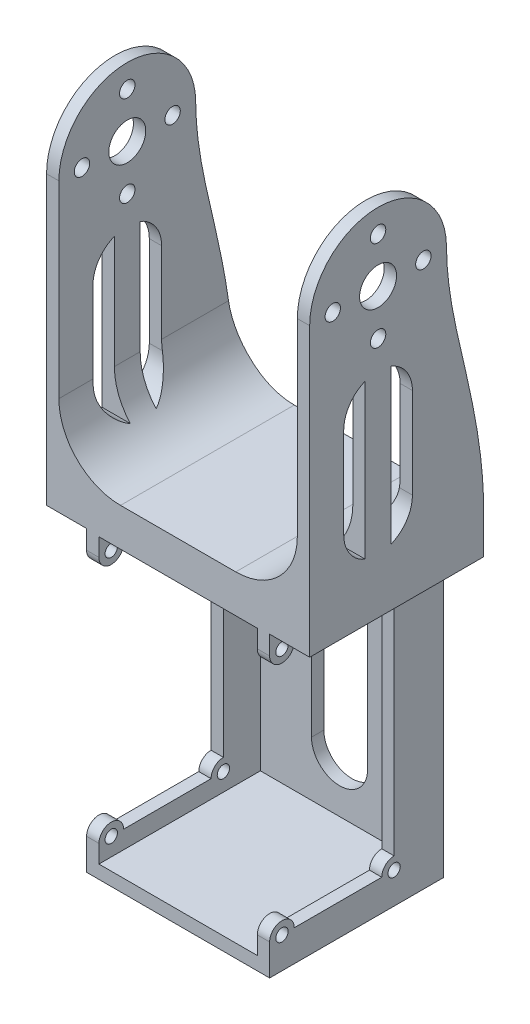
SolidWorks part; units mm, degrees
ref_plane "前视基准面" through (0, 0, 0) normal (0, 0, 1) x (1, 0, 0)
ref_plane "上视基准面" through (0, 0, 0) normal (0, 1, 0) x (1, 0, 0)
ref_plane "右视基准面" through (0, 0, 0) normal (1, 0, 0) x (0, 0, -1)
other "Configuration Table"
sketch "草图1" plane through (0, 0, 0) normal (0, 1, 0) x (1, 0, 0)
  line L0 (0, 10.5) -> (0, -10.5) construction
  line L1 (-21.35, 10.5) -> (21.35, 10.5)
  line L2 (-21.35, 10.5) -> (-21.35, -10.5)
  line L3 (-21.35, -10.5) -> (21.35, -10.5)
  line L4 (21.35, 10.5) -> (21.35, -10.5)
  line L5 (-21.35, 10.5) -> (21.35, -10.5) construction
  line L6 (-21.35, -10.5) -> (21.35, 10.5) construction
  line L7 (-21.35, 0) -> (21.35, 0) construction
  line L8 (8.018, 1.5509) -> (12.9126, 1.5509)
  line L9 (8.018, -1.5509) -> (12.9126, -1.5509)
  line L10 (-8.018, -1.5509) -> (-12.9126, -1.5509)
  line L11 (-8.018, 1.5509) -> (-12.9126, 1.5509)
  circle A0 centre (7.5, 5) radius 1.5
  arc A1 (12.9126, 1.5509) -> (14.6975, 0) centre (13.0296, -0.117) cw
  arc A2 (12.9126, -1.5509) -> (14.6975, 0) centre (13.0296, 0.117) ccw
  circle A3 centre (7.5, -5) radius 1.5
  circle A4 centre (-7.5, -5) radius 1.5
  arc A5 (-12.9126, -1.5509) -> (-14.6975, 0) centre (-13.0296, 0.117) cw
  arc A6 (-12.9126, 1.5509) -> (-14.6975, 0) centre (-13.0296, -0.117) ccw
  circle A7 centre (-7.5, 5) radius 1.5
  spline S0 degree 3 poles (0, 7.4073) (2.0925, 7.358) (3.0437, 2.9519) (6.0077, 1.6267) (8.018, 1.5509) knots 0 0 0 0 0.496823 1 1 1 1
  spline S1 degree 3 poles (0, -7.4073) (2.0925, -7.358) (3.0437, -2.9519) (6.0077, -1.6267) (8.018, -1.5509) knots 0 0 0 0 0.496823 1 1 1 1
  spline S2 degree 3 poles (0, -7.4073) (-2.0925, -7.358) (-3.0437, -2.9519) (-6.0077, -1.6267) (-8.018, -1.5509) knots 0 0 0 0 0.496823 1 1 1 1
  spline S3 degree 3 poles (0, 7.4073) (-2.0925, 7.358) (-3.0437, 2.9519) (-6.0077, 1.6267) (-8.018, 1.5509) knots 0 0 0 0 0.496823 1 1 1 1
  point P0 (0, 0)
  point P6 (7.5, 5)
  point P13 (0, 7.4073)
  point P14 (2.4183, 5.7294)
  point P15 (3.5345, 3.7404)
  point P16 (4.8936, 2.4067)
  point P17 (8.018, 1.5509)
  dimension "D5" = 3
  dimension "D1" = 21
  dimension "D2" = 42.7
  dimension "D3" = 7.5
  dimension "D4" = 5
extrude "凸台-拉伸1" add sketch "草图1" along normal blind 2
sketch "草图2" plane through (-21.35, 0, 0) normal (-1, 0, 0) x (0, 0, 1)
  line L0 (-10.5, 2) -> (-10.5, 46)
  line L1 (10.5, 2) -> (10.5, 46)
  line L2 (-10.5, 46) -> (10.5, 46) construction
  line L3 (0, 46) -> (0, 56.5) construction
  line L4 (-10.5, 2) -> (10.5, 2)
  line L5 (0, 46) -> (0, 38.65) construction
  line L6 (-2.0914, 33.7195) -> (-2.0914, 8.6826)
  line L7 (0, 28.5519) -> (0, 13.8502) construction
  line L8 (5.5747, 28.5519) -> (5.5747, 13.8502)
  line L9 (-5.5747, 28.5519) -> (-5.5747, 13.8502)
  line L10 (2.0914, 33.7195) -> (2.0914, 8.6826)
  arc A0 (-10.5, 46) -> (10.5, 46) centre (0, 46) cw
  circle A1 centre (0, 38.65) radius 1.25
  circle A2 centre (-7.35, 46) radius 1.25
  circle A3 centre (0, 53.35) radius 1.25
  circle A4 centre (7.35, 46) radius 1.25
  circle A5 centre (0, 46) radius 3
  arc A6 (5.5747, 28.5519) -> (2.0914, 33.7195) centre (0, 28.5519) ccw
  arc A7 (-5.5747, 13.8502) -> (-2.0914, 8.6826) centre (0, 13.8502) ccw
  arc A8 (-2.0914, 33.7195) -> (-5.5747, 28.5519) centre (0, 28.5519) ccw
  arc A9 (2.0914, 8.6826) -> (5.5747, 13.8502) centre (0, 13.8502) ccw
  point P12 (-7.35, 46)
  point P13 (7.35, 46)
  point P14 (0, 53.35)
  point P24 (0, 21.201)
  point P29 (-2.0914, 33.7195)
  dimension "D5" = 2.5
  dimension "D9" = 2.5
  dimension "D10" = 2.5
  dimension "D11" = 2.5
  dimension "D12" = 6
  dimension "D1" = 44
  dimension "D2" = 44
  dimension "D3" = 10.5
  dimension "D4" = 7.35
  dimension "D6" = 7.35
  dimension "D7" = 7.35
  dimension "D8" = 7.35
extrude "凸台-拉伸2" add sketch "草图2" against normal blind 2
mirror "镜向1" about plane through (0, 0, 0) normal (1, 0, 0) of "凸台-拉伸2"
sketch "草图3" plane through (0, 0, 0) normal (1, 0, 0) x (0, 0, -1)
  line L0 (0, 0) -> (0, -3.6619)
  line L1 (0, -3.6619) -> (9.1, -3.6619) construction
  line L2 (0, -3.6619) -> (-9.1, -3.6619) construction
  line L3 (-11.1, -3.6619) -> (-11.1, 0)
  line L4 (11.1, -3.6619) -> (11.1, 0)
  line L5 (11.1, 0) -> (-11.1, 0)
  line L6 (-7.1, -3.6619) -> (7.1, -3.6619)
  circle A0 centre (-9.1, -3.6619) radius 1
  circle A1 centre (9.1, -3.6619) radius 1
  arc A2 (-11.1, -3.6619) -> (-7.1, -3.6619) centre (-9.1, -3.6619) ccw
  arc A3 (7.1, -3.6619) -> (11.1, -3.6619) centre (9.1, -3.6619) ccw
  circle A4 centre (-9.1, -3.6619) radius 2 construction
  circle A5 centre (9.1, -3.6619) radius 2 construction
  dimension "D3" = 2
  dimension "D4" = 2
  dimension "D1" = 9.1
  dimension "D2" = 9.1
  dimension "D5" = 1
  dimension "D6" = 1
extrude "凸台-拉伸3" add sketch "草图3" along normal blind 14.85 and the other way blind 14.85 contours L3 A2 L6 L0 L5 A0 | L6 A3 L4 L5 L0 A1 region at (0, -2.0841, -5.8047) region at (0, -2.0841, 5.8047)
sketch "草图4" plane through (-21.35, 0, 0) normal (-1, 0, 0) x (0, 0, 1)
  line L3 (2.0914, 33.7195) -> (2.0914, 8.6826) construction
  line L4 (5.5747, 13.8502) -> (5.5747, 28.5519) construction
  line L5 (-5.5747, 28.5519) -> (-5.5747, 13.8502) construction
  line L6 (-11.1, -0.6) -> (11.1, -0.6)
  line L7 (11.1, -0.6) -> (11.1, 46)
  line L8 (-11.1, 46) -> (-11.1, -0.6)
  line L9 (-11.1, -0.6) -> (11.1, -0.6)
  line L10 (11.1, -0.6) -> (11.1, 46)
  line L11 (-11.1, 46) -> (-11.1, -0.6)
  line L12 (-5.5747, 28.5519) -> (-5.5747, 13.8502)
  line L13 (5.5747, 13.8502) -> (5.5747, 28.5519)
  line L14 (2.0914, 33.7195) -> (2.0914, 8.6826)
  line L15 (-2.0914, 8.6826) -> (-2.0914, 33.7195) construction
  line L16 (-2.0914, 8.6826) -> (-2.0914, 33.7195)
  circle A1 centre (-7.35, 46) radius 1.25 construction
  arc A2 (11.1, 46) -> (-11.1, 46) centre (0, 46) ccw
  arc A3 (11.1, 46) -> (-11.1, 46) centre (0, 46) ccw
  circle A4 centre (-7.35, 46) radius 1.25
  circle A5 centre (0, 53.35) radius 1.25 construction
  circle A6 centre (0, 53.35) radius 1.25
  circle A7 centre (7.35, 46) radius 1.25 construction
  circle A8 centre (7.35, 46) radius 1.25
  circle A9 centre (0, 38.65) radius 1.25 construction
  circle A10 centre (0, 38.65) radius 1.25
  arc A11 (5.5747, 28.5519) -> (2.0914, 33.7195) centre (0, 28.5519) ccw construction
  arc A12 (2.0914, 8.6826) -> (5.5747, 13.8502) centre (0, 13.8502) ccw construction
  arc A13 (-2.0914, 33.7195) -> (-5.5747, 28.5519) centre (0, 28.5519) ccw construction
  arc A14 (-5.5747, 13.8502) -> (-2.0914, 8.6826) centre (0, 13.8502) ccw construction
  arc A15 (-5.5747, 13.8502) -> (-2.0914, 8.6826) centre (0, 13.8502) ccw
  arc A16 (-2.0914, 33.7195) -> (-5.5747, 28.5519) centre (0, 28.5519) ccw
  arc A17 (2.0914, 8.6826) -> (5.5747, 13.8502) centre (0, 13.8502) ccw
  arc A18 (5.5747, 28.5519) -> (2.0914, 33.7195) centre (0, 28.5519) ccw
  circle A19 centre (0, 46) radius 3
  dimension "D1" = 0.6
extrude "凸台-拉伸5" add sketch "草图4" against normal blind 2
mirror "镜向2" about plane through (0, 0, 0) normal (1, 0, 0) of "凸台-拉伸5"
sketch "草图5" plane through (0, 0, 11.1) normal (0, 0, 1) x (1, 0, 0)
  line L3 (-19.35, -0.6) -> (-19.35, 5.4)
  line L4 (-19.35, -0.6) -> (-19.35, 46) construction
  line L5 (-19.35, 5.4) -> (19.35, 5.4)
  line L6 (19.35, -0.6) -> (19.35, 46) construction
  line L7 (19.35, 5.4) -> (19.35, -0.6)
  line L8 (-19.35, -0.6) -> (19.35, -0.6)
  dimension "D1" = 6
extrude "凸台-拉伸7" add sketch "草图5" against normal up to surface (22.2 mm away) up to face at (20.35, 22.7, -11.1)
fillet "圆角1" radius 10 2 edges at (19.35, 5.4, 0) (-19.35, 5.4, 0)
sketch "草图7" plane through (14.85, 0, 0) normal (1, 0, 0) x (0, 0, -1)
  line L0 (-9.1, -3.6619) -> (9.1, -3.6619) construction
  line L1 (0, -3.6619) -> (0, -43.8619)
  line L2 (0, -23.7619) -> (7.0616, -23.7619) construction
  line L3 (11.1, -43.8619) -> (11.1, -46.9238)
  line L4 (-11.1, -43.8619) -> (-11.1, -46.9238)
  line L5 (-7.1, -43.8619) -> (7.1, -43.8619)
  line L6 (11.1, -3.6619) -> (11.1, -0.6) construction
  line L7 (11.1, -3.6619) -> (11.1, -0.6)
  line L8 (-11.1, -3.6619) -> (-11.1, -0.6) construction
  line L9 (-11.1, -3.6619) -> (-11.1, -0.6)
  line L10 (-11.1, -46.9238) -> (11.1, -46.9238)
  line L11 (15.1, -43.8619) -> (15.1, -3.6619)
  line L12 (17.1, -3.6619) -> (17.1, -43.8619)
  line L13 (11.1, -0.6) -> (17.1, -0.6)
  line L14 (17.1, -0.6) -> (17.1, -3.6619)
  line L15 (17.1, -43.8619) -> (17.1, -46.9238)
  line L16 (17.1, -46.9238) -> (11.1, -46.9238)
  line L17 (15.1, -43.8619) -> (11.1, -43.8619)
  line L18 (15.1, -3.6619) -> (11.1, -3.6619)
  line L19 (11.1, -0.6) -> (11.1, -3.6619)
  circle A0 centre (-9.1, -3.6619) radius 1 construction
  circle A1 centre (-9.1, -3.6619) radius 1
  circle A2 centre (9.1, -43.8619) radius 1
  circle A3 centre (-9.1, -43.8619) radius 1
  circle A4 centre (9.1, -3.6619) radius 1 construction
  circle A5 centre (9.1, -3.6619) radius 1
  arc A6 (7.1, -3.6619) -> (11.1, -3.6619) centre (9.1, -3.6619) ccw construction
  arc A7 (7.1, -3.6619) -> (11.1, -3.6619) centre (9.1, -3.6619) ccw
  arc A8 (-11.1, -3.6619) -> (-7.1, -3.6619) centre (-9.1, -3.6619) ccw construction
  arc A9 (-11.1, -3.6619) -> (-7.1, -3.6619) centre (-9.1, -3.6619) ccw
  arc A10 (7.1, -43.8619) -> (11.1, -43.8619) centre (9.1, -43.8619) cw
  arc A11 (-11.1, -43.8619) -> (-7.1, -43.8619) centre (-9.1, -43.8619) cw
  line M11 (11.1, -3.6619) -> (11.1, -0.6)
  dimension "D1" = 40.2
  dimension "D2" = 6
  dimension "D3" = 2
extrude "凸台-拉伸9" add sketch "草图7" against normal up to surface (29.7 mm away) contours L18 L11 L17 L3 L16 L15 L12 L14 L13 M11 | A11 L4 L10 L3 A10 L5 A2 A3 region at (14.85, -23.7619, -15.4727) region at (14.85, -45.1197, 0) up to face at (-14.85, -3.6619, 8.1)
sketch "草图8" plane through (14.85, 0, 0) normal (1, 0, 0) x (0, 0, -1)
  line L0 (15.1, -43.8619) -> (11.1, -43.8619) construction
  line L1 (15.1, -43.8619) -> (15.1, -3.6619) construction
  line L2 (15.1, -3.6619) -> (11.1, -3.6619) construction
  line L3 (15.1, -43.8619) -> (11.1, -43.8619)
  line L4 (15.1, -43.8619) -> (15.1, -3.6619)
  line L5 (15.1, -3.6619) -> (11.1, -3.6619)
  line L6 (9.1, -5.6619) -> (9.1, -41.8619)
  arc A0 (11.1, -43.8619) -> (7.1, -43.8619) centre (9.1, -43.8619) ccw construction
  arc A1 (7.1, -3.6619) -> (11.1, -3.6619) centre (9.1, -3.6619) ccw construction
  arc A2 (11.1, -43.8619) -> (9.1, -41.8619) centre (9.1, -43.8619) ccw
  arc A3 (9.1, -5.6619) -> (11.1, -3.6619) centre (9.1, -3.6619) ccw
extrude "凸台-拉伸10" add sketch "草图8" against normal blind 2
mirror "镜向3" about plane through (0, 0, 0) normal (1, 0, 0) of "凸台-拉伸10"
sketch "草图9" plane through (0, 0, 11.1) normal (0, 0, 1) x (1, 0, 0)
  line L0 (-12.85, -3.6619) -> (-12.85, -0.7619)
  line L1 (-14.85, -3.6619) -> (14.85, -3.6619) construction
  line L2 (-12.85, -43.8619) -> (-12.85, -3.6619) construction
  line L3 (12.85, -3.6619) -> (12.85, -0.7619)
  line L4 (12.85, -43.8619) -> (12.85, -3.6619) construction
  line L5 (-12.85, -0.7619) -> (12.85, -0.7619)
  line L6 (-12.85, -43.8619) -> (-12.85, -46.7619)
  line L7 (-14.85, -43.8619) -> (14.85, -43.8619) construction
  line L8 (-12.85, -46.7619) -> (12.85, -46.7619)
  line L9 (12.85, -46.7619) -> (12.85, -43.8619)
  line L10 (-12.85, -3.6619) -> (-12.85, -43.8619)
  line L11 (12.85, -3.6619) -> (12.85, -43.8619)
  dimension "D1" = 2.9
  dimension "D2" = 2.9
  dimension "D3" = 2.9
extrude "切除-拉伸2" cut sketch "草图9" against normal up to surface (26.2 mm away) up to face at (0, -23.7619, -15.1)
sketch "草图10" plane through (0, -46.9238, 0) normal (0, -1, 0) x (1, 0, 0)
  line L4 (14.85, 11.1) -> (-14.85, 11.1)
  line L5 (-14.85, 11.1) -> (-14.85, -17.1)
  line L6 (-14.85, -17.1) -> (14.85, -17.1)
  line L7 (14.85, -17.1) -> (14.85, 11.1)
  line L8 (14.85, 11.1) -> (-14.85, 11.1)
  line L9 (-14.85, 11.1) -> (-14.85, -17.1)
  line L10 (-14.85, -17.1) -> (14.85, -17.1)
  line L11 (14.85, -17.1) -> (14.85, 11.1)
  dimension "D1" = 0
extrude "凸台-拉伸11" add sketch "草图10" along normal blind 2
sketch "草图11" plane through (0, 0, -11.1) normal (0, 0, -1) x (-1, 0, 0)
  line L10 (-21.35, -0.6) -> (-14.85, -0.6)
  line L11 (-14.85, -0.6) -> (14.85, -0.6)
  line L12 (14.85, -0.6) -> (21.35, -0.6)
  line L13 (21.35, -0.6) -> (21.35, 46)
  line L14 (21.35, 46) -> (19.35, 46)
  line L15 (19.35, 46) -> (19.35, 15.4)
  line L16 (9.35, 5.4) -> (-9.35, 5.4)
  line L17 (-19.35, 15.4) -> (-19.35, 46)
  line L18 (-19.35, 46) -> (-21.35, 46)
  line L19 (-21.35, 46) -> (-21.35, -0.6)
  line L20 (-21.35, -0.6) -> (-14.85, -0.6)
  line L21 (-14.85, -0.6) -> (14.85, -0.6)
  line L22 (14.85, -0.6) -> (21.35, -0.6)
  line L23 (21.35, -0.6) -> (21.35, 46)
  line L24 (21.35, 46) -> (19.35, 46)
  line L25 (19.35, 46) -> (19.35, 15.4)
  line L26 (9.35, 5.4) -> (-9.35, 5.4)
  line L27 (-19.35, 15.4) -> (-19.35, 46)
  line L28 (-19.35, 46) -> (-21.35, 46)
  line L29 (-21.35, 46) -> (-21.35, -0.6)
  arc A2 (9.35, 5.4) -> (19.35, 15.4) centre (9.35, 15.4) ccw
  arc A3 (-19.35, 15.4) -> (-9.35, 5.4) centre (-9.35, 15.4) ccw
  arc A4 (9.35, 5.4) -> (19.35, 15.4) centre (9.35, 15.4) ccw
  arc A5 (-19.35, 15.4) -> (-9.35, 5.4) centre (-9.35, 15.4) ccw
  dimension "D1" = 0
extrude "凸台-拉伸12" add sketch "草图11" along normal up to surface (6 mm away) up to face at (0, -24.7619, -17.1)
sketch "草图12" plane through (21.35, 0, 0) normal (1, 0, 0) x (0, 0, -1)
  line L0 (17.1, -0.6) -> (17.1, 46) construction
  line L1 (11.1, 46) -> (17.1, 46)
  line L2 (17.1, 46) -> (17.1, 7.9142)
  spline S0 degree 3 poles (11.1, 46) (11.1502, 39.3995) (14.4458, 26.89) (16.8816, 14.2557) (17.1, 7.9142) knots 0 0 0 0 0.509578 1 1 1 1
extrude "切除-拉伸3" cut sketch "草图12" against normal up to surface (42.7 mm away) up to face at (-21.35, 21.201, -4.2279)
sketch "草图13" plane through (0, 0, -17.1) normal (0, 0, -1) x (-1, 0, 0)
  line L0 (0, -6.3847) -> (0, -37.8754)
  line L1 (0, -6.3847) -> (0, -37.8754) construction
  line L2 (4.5505, -6.3847) -> (4.5505, -37.8754)
  line L3 (-4.5505, -6.3847) -> (-4.5505, -37.8754)
  arc A0 (4.5505, -6.3847) -> (-4.5505, -6.3847) centre (0, -6.3847) ccw
  arc A1 (-4.5505, -37.8754) -> (4.5505, -37.8754) centre (0, -37.8754) ccw
  point P3 (0, -22.13)
extrude "切除-拉伸4" cut sketch "草图13" against normal blind 2 contours L3 A1 L2 A0 region at (-4.1345, -22.13, -17.1)
